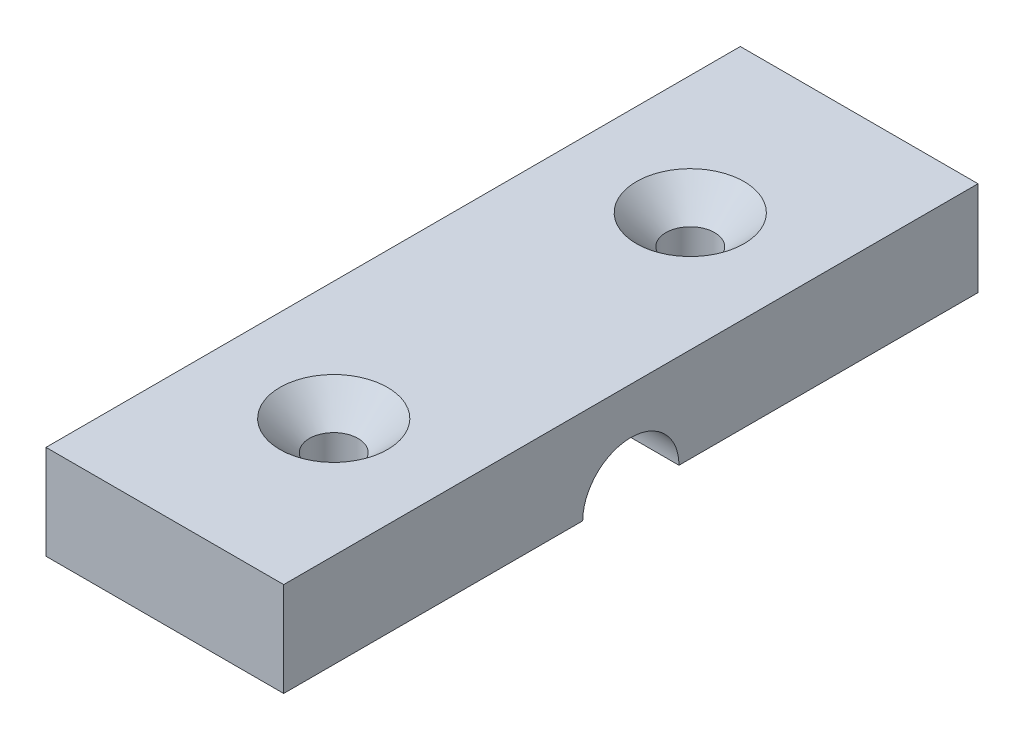
SolidWorks part; units mm, degrees
ref_plane "Top Plane" through (0, 0, 0) normal (0, 0, 1) x (1, 0, 0)
ref_plane "Front Plane" through (0, 0, 0) normal (0, 1, 0) x (1, 0, 0)
ref_plane "Right Plane" through (0, 0, 0) normal (1, 0, 0) x (0, 0, -1)
sketch "Sketch1" plane through (0, -110.0687, 0) normal (0, 1, 0) x (1, 0, 0)
  line L1 (88.3339, -91.8373) -> (68.3339, -91.8373)
  line L2 (88.3339, -91.8373) -> (88.3339, -33.4173)
  line L3 (88.3339, -33.4173) -> (68.3339, -33.4173)
  line L4 (68.3339, -91.8373) -> (68.3339, -33.4173)
  circle A0 centre (78.3339, -77.6273) radius 2.05
  circle A1 centre (78.3339, -47.6273) radius 2.05
  circle A2 centre (78.3339, -77.6273) radius 1.625 construction
  circle A3 centre (78.3339, -47.6273) radius 1.625 construction
  point P20 (78.3339, -91.8373)
  dimension "D2" = 4.1
extrude "Boss-Extrude1" add sketch "Sketch1" along normal blind 7.9375
extrude "Cut-Extrude1" cut sketch "Sketch2" against normal blind 15
sketch "Sketch2" plane through (88.3339, -1.5875, 4.9363) normal (1, 0, 0) x (0, 0, -1)
  circle A0 centre (-57.691, -108.4812) radius 4.05
  point P2 (-59.8912, -131.6563)
  point P3 (0, 0)
  point P6 (-40.0342, -108.4812)
  point P9 (0, 0)
chamfer "Chamfer1" distance 2.48 angle 45 2 edges at (78.3339, -102.1312, 49.6773) (78.3339, -102.1312, 79.6773)
